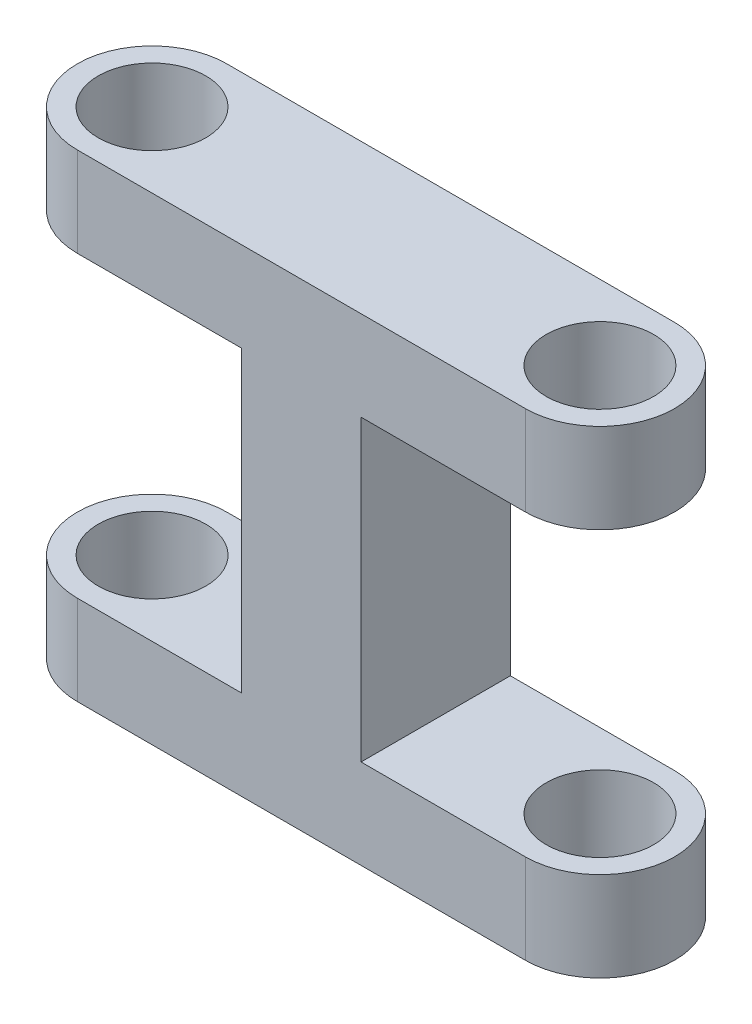
SolidWorks part; units mm, degrees
ref_plane "前视基准面" through (0, 0, 0) normal (0, 0, 1) x (1, 0, 0)
ref_plane "上视基准面" through (0, 0, 0) normal (0, 1, 0) x (1, 0, 0)
ref_plane "右视基准面" through (0, 0, 0) normal (1, 0, 0) x (0, 0, -1)
other "Configuration Table"
sketch "草图1" plane through (0, 0, 0) normal (0, 1, 0) x (1, 0, 0)
  line L0 (0, -4) -> (9976.5942, -4) construction
  line L1 (4, -1.5) -> (19, -1.5)
  line L3 (4, -6.5) -> (19, -6.5)
  line L5 (11.5, 0) -> (11.5, -9976.5942) construction
  circle A0 centre (4, -4) radius 1.8
  circle A1 centre (4, -4) radius 2.5
  circle A2 centre (19, -4) radius 2.5
  circle A3 centre (19, -4) radius 1.8
  point P10 (11.5, -1.5)
  dimension "D1" = 3.6
  dimension "D2" = 5
  dimension "D3" = 15
extrude "凸台-拉伸1" add sketch "草图1" along normal blind 16 contours L3 A2 L1 A1 | A1 A0 | A2 A3 region at (11.5, 0, 4) region at (5.7178, 0, 2.2822) region at (20.7178, 0, 2.2822)
sketch "草图2" plane through (0, 0, 6.5) normal (0, 0, 1) x (1, 0, 0)
  line L0 (11.5, 16) -> (11.5, -49984) construction
  line L1 (4, 16) -> (19, 16) construction
  line L2 (0, 8) -> (50000, 8) construction
  line L3 (1.5, 16) -> (1.5, 0) construction
  line L4 (13.5, 13) -> (13.5, 3)
  line L5 (1.5, 13) -> (9.5, 13)
  line L6 (1.5, 13) -> (1.5, 3)
  line L7 (1.5, 3) -> (9.5, 3)
  line L8 (9.5, 13) -> (9.5, 3)
  line L9 (21.5, 3) -> (13.5, 3)
  line L10 (21.5, 13) -> (21.5, 3)
  line L11 (21.5, 13) -> (13.5, 13)
  point P4 (11.5, 16)
  point P9 (1.5, 8)
  point P14 (9.5, 8)
  dimension "D1" = 10
  dimension "D2" = 8
extrude "切除-拉伸1" cut sketch "草图2" against normal up to next
